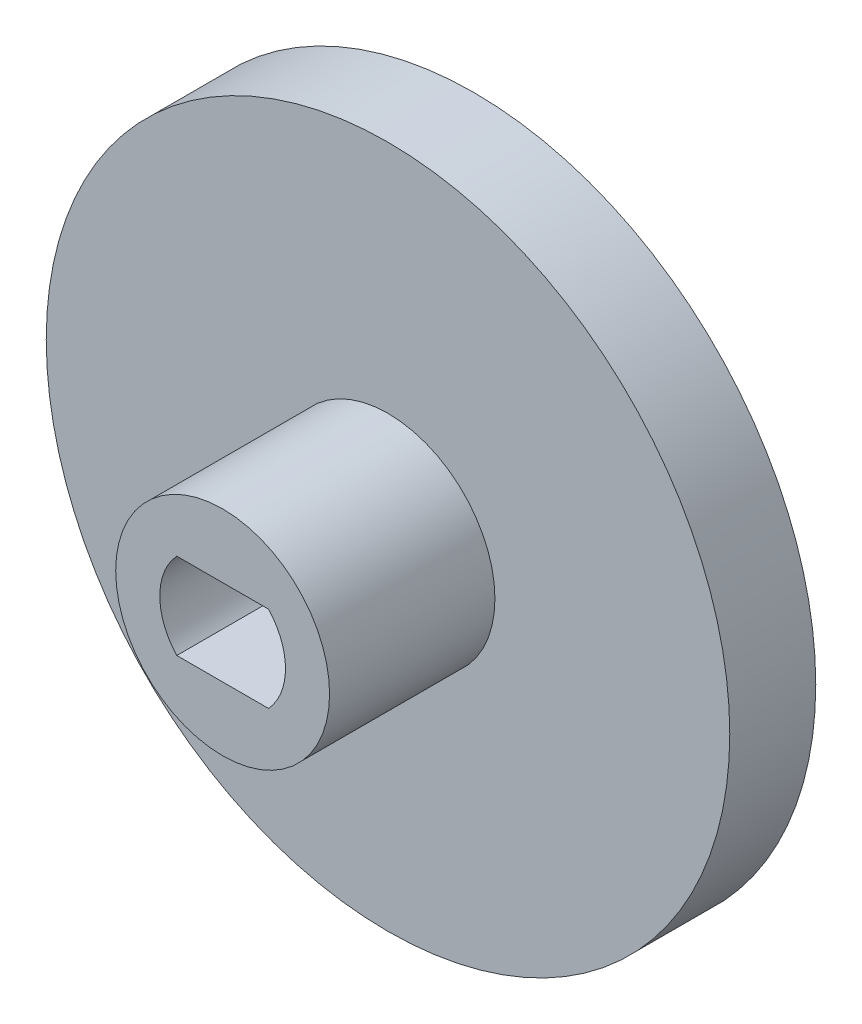
SolidWorks part; units mm, degrees
ref_plane "Front Plane" through (0, 0, 0) normal (0, 0, 1) x (1, 0, 0)
ref_plane "Top Plane" through (0, 0, 0) normal (0, 1, 0) x (1, 0, 0)
ref_plane "Right Plane" through (0, 0, 0) normal (1, 0, 0) x (0, 0, -1)
sketch "Sketch1" plane through (0, 0, 0) normal (0, 0, 1) x (1, 0, 0)
  circle A0 centre (0, 0) radius 15.5 construction
  circle A1 centre (0, 0) radius 15.5
extrude "Boss-Extrude1" add sketch "Sketch1" along normal blind 3
sketch "Sketch2" plane through (0, 0, 0) normal (0, 0, -1) x (-1, 0, 0)
  line L0 (-7.8174, 8.129) -> (-3.5527, 4.927)
  line L1 (0.2749, 6.0681) -> (2.0901, 11.0826)
  line L2 (-7.8774, 8.0491) -> (-3.6127, 4.8471)
  line L3 (0.3689, 6.0341) -> (2.1842, 11.0485)
  line L4 (-7.8774, 8.0491) -> (-3.6127, 4.8471) construction
  line L5 (0.3689, 6.0341) -> (2.1842, 11.0485) construction
  arc A0 (1.3416, 12.2836) -> (-7.8486, 9.5439) centre (0, 0) ccw
  arc A1 (-7.8486, 9.5439) -> (-7.8174, 8.129) centre (-7.277, 8.8488) ccw
  arc A2 (-3.5527, 4.927) -> (-2.5887, 4.8527) centre (-3.0123, 5.6468) ccw
  arc A3 (-0.491, 5.478) -> (-2.5887, 4.8527) centre (0, 0) ccw
  arc A4 (-0.491, 5.478) -> (0.2749, 6.0681) centre (-0.5714, 6.3744) ccw
  arc A5 (2.0901, 11.0826) -> (1.3416, 12.2836) centre (1.2439, 11.3889) ccw
  arc A6 (1.3524, 12.383) -> (-7.9122, 9.6211) centre (0, 0) ccw
  arc A7 (-7.9122, 9.6211) -> (-7.8774, 8.0491) centre (-7.277, 8.8488) ccw
  arc A8 (-3.6127, 4.8471) -> (-2.5416, 4.7645) centre (-3.0123, 5.6468) ccw
  arc A9 (-0.4821, 5.3784) -> (-2.5416, 4.7645) centre (0, 0) ccw
  arc A10 (-0.4821, 5.3784) -> (0.3689, 6.0341) centre (-0.5714, 6.3744) ccw
  arc A11 (2.1842, 11.0485) -> (1.3524, 12.383) centre (1.2439, 11.3889) ccw
  arc A12 (1.3524, 12.383) -> (-7.9122, 9.6211) centre (0, 0) ccw construction
  arc A13 (-7.9122, 9.6211) -> (-7.8774, 8.0491) centre (-7.277, 8.8488) ccw construction
  arc A14 (-3.6127, 4.8471) -> (-2.5416, 4.7645) centre (-3.0123, 5.6468) ccw construction
  arc A15 (-0.4821, 5.3784) -> (-2.5416, 4.7645) centre (0, 0) ccw construction
  arc A16 (-0.4821, 5.3784) -> (0.3689, 6.0341) centre (-0.5714, 6.3744) ccw construction
  arc A17 (2.1842, 11.0485) -> (1.3524, 12.383) centre (1.2439, 11.3889) ccw construction
  dimension "D1" = 0
  dimension "D2" = 0.1
extrude "Boss-Extrude2" add sketch "Sketch2" along normal offset from surface (1.9 mm away) 0.3
pattern_circular "CirPattern1" count 5 over 360 about axis through (0, 0, 3) along (0, 0, -1) of "Boss-Extrude2"
sketch "Sketch3" plane through (0, 0, 3) normal (0, 0, 1) x (1, 0, 0)
  circle A0 centre (0, 0) radius 4.85
  dimension "D1" = 9.7
extrude "Boss-Extrude3" add sketch "Sketch3" along normal blind 7.5
sketch "Sketch4" plane through (0, 0, 0) normal (0, 0, 1) x (1, 0, 0)
  circle A0 centre (0, 0) radius 2
  dimension "D1" = 4
extrude "Cut-Extrude1" cut sketch "Sketch4" along normal offset from surface (3 mm away) 7.5 up to face at (4.85, 0, 10.5)
sketch "Sketch5" plane through (0, 0, 10.5) normal (0, 0, 1) x (1, 0, 0)
  line L0 (-2.0785, 1.95) -> (2.0785, 1.95)
  line L1 (2.0785, -1.95) -> (-2.0785, -1.95)
  arc A0 (-2.0785, 1.95) -> (-2.0785, -1.95) centre (0, 0) ccw
  arc A1 (2.0785, -1.95) -> (2.0785, 1.95) centre (0, 0) ccw
  point P7 (0, 0)
  dimension "D1" = 5.7
  dimension "D2" = 3.9
extrude "Cut-Extrude2" cut sketch "Sketch5" against normal up to surface (7.5 mm away) up to face at (2, 0, 3)
sketch "Sketch6" plane through (0, 0, 0) normal (0, 0, -1) x (-1, 0, 0)
  circle A1 centre (0, 0) radius 15.5 construction
  circle A2 centre (0, 0) radius 15.5
  circle A3 centre (0, 0) radius 13.5
  dimension "D1" = 2
extrude "Boss-Extrude4" add sketch "Sketch6" along normal offset from surface (0.9 mm away) 0.1
